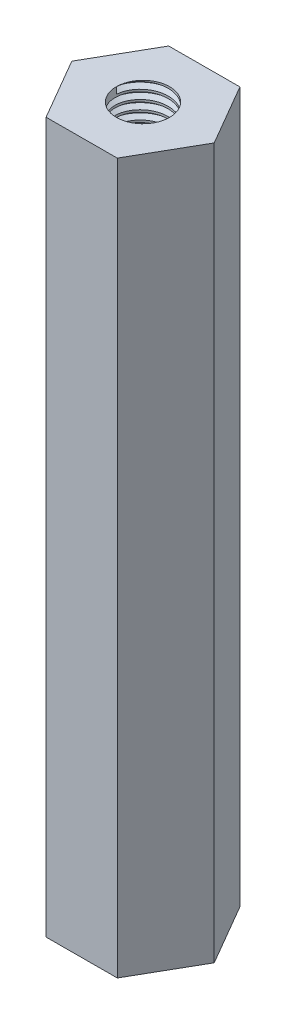
SolidWorks part; units mm, degrees
ref_plane "前视基准面" through (0, 0, 0) normal (0, 0, 1) x (1, 0, 0)
ref_plane "上视基准面" through (0, 0, 0) normal (0, 1, 0) x (1, 0, 0)
ref_plane "右视基准面" through (0, 0, 0) normal (1, 0, 0) x (0, 0, -1)
sketch "草图1" plane through (0, 0, 0) normal (0, 1, 0) x (1, 0, 0)
  line L1 (2.0098, -3.4584) -> (4, 0.0114)
  line L2 (4, 0.0114) -> (1.9902, 3.4698)
  line L3 (1.9902, 3.4698) -> (-2.0098, 3.4584)
  line L4 (-2.0098, 3.4584) -> (-4, -0.0114)
  line L5 (-4, -0.0114) -> (-1.9902, -3.4698)
  line L6 (-1.9902, -3.4698) -> (2.0098, -3.4584)
  circle A0 centre (0, 0) radius 3.4641 construction
  dimension "D1" = 4
extrude "凸台-拉伸1" add sketch "草图1" along normal blind 40
sketch "草图2" plane through (0, 0, 0) normal (0, -1, 0) x (1, 0, 0)
  circle A0 centre (0, 0) radius 1.5
  dimension "D1" = 3
extrude "切除-拉伸1" cut sketch "草图2" against normal blind 10
sketch "草图3" plane through (0, 40, 0) normal (0, 1, 0) x (1, 0, 0)
  circle A0 centre (0, 0) radius 1.5
  dimension "D1" = 3
extrude "切除-拉伸2" cut sketch "草图3" against normal blind 10
thread "螺纹线1" pitch 0.5 method cut profile "螺纹线轮廓1" start angle 0, offset 0, length 8, pitch 0.5, diameter 3
ref_plane "基准面1" through (1.5, 0, 0) normal (0, 0, 1) x (1, 0, 0)
sketch "螺纹线轮廓1" plane through (1.5, 0, 0) normal (0, 0, 1) x (1, 0, 0)
  line L0 (0, 0) -> (0, 0.5) construction
  line L1 (0, 0) -> (0.2706, 0.1562)
  line L2 (0.2706, 0.1562) -> (0.2706, 0.2187)
  line L3 (0.2706, 0.2187) -> (0, 0.375)
  line L4 (0.2706, 0.1875) -> (0, 0.1875) construction
  line L11 (0, 0) -> (0, 0.375)
  point P2 (0, 0)
  dimension "Pitch" = 0.5
  dimension "Profile_Angle" = 60
  dimension "Profile_Land" = 0.0625
  dimension "Profile_Height" = 0.2706
thread "螺纹线2" pitch 0.5 method cut profile "螺纹线轮廓2" start angle 0, offset 0, length 8, pitch 0.5, diameter 3
ref_plane "基准面2" through (-1.5, 40, 0) normal (0, 0, 1) x (-1, 0, 0)
sketch "螺纹线轮廓2" plane through (-1.5, 40, 0) normal (0, 0, 1) x (-1, 0, 0)
  line L0 (0, 0) -> (0, 0.5) construction
  line L1 (0, 0) -> (0.2706, 0.1562)
  line L2 (0.2706, 0.1562) -> (0.2706, 0.2187)
  line L3 (0.2706, 0.2187) -> (0, 0.375)
  line L4 (0.2706, 0.1875) -> (0, 0.1875) construction
  line L11 (0, 0) -> (0, 0.375)
  point P2 (0, 0)
  dimension "Pitch" = 0.5
  dimension "Profile_Angle" = 60
  dimension "Profile_Land" = 0.0625
  dimension "Profile_Height" = 0.2706
